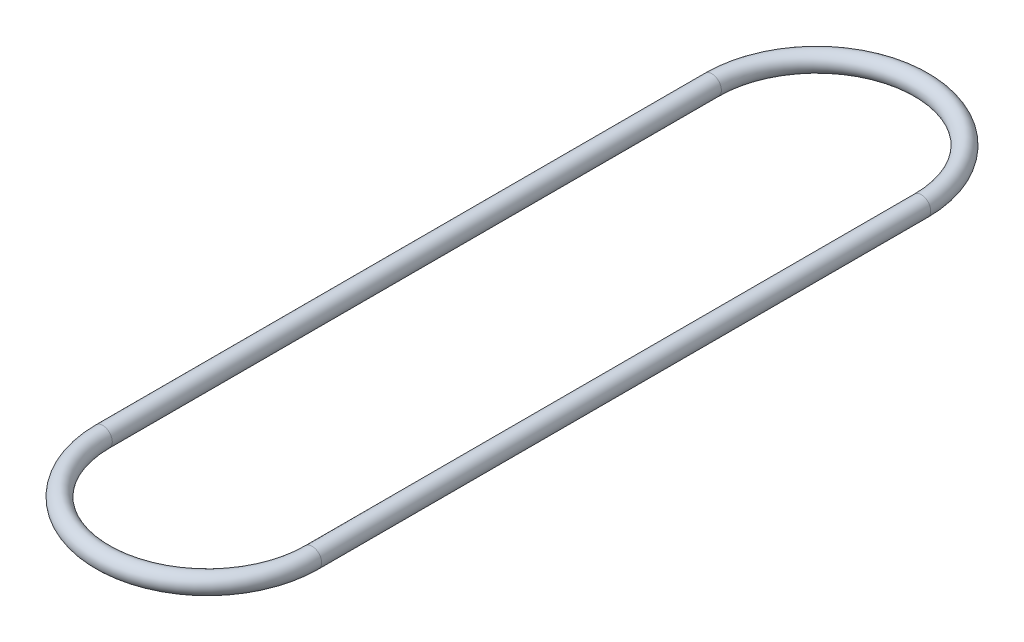
SolidWorks part; units mm, degrees
ref_plane "Front" through (0, 0, 0) normal (0, 0, 1) x (1, 0, 0)
ref_plane "Top" through (0, 0, 0) normal (0, 1, 0) x (1, 0, 0)
ref_plane "Right" through (0, 0, 0) normal (1, 0, 0) x (0, 0, -1)
sketch "Sketch1" plane through (0, 0, 0) normal (0, 0, 1) x (1, 0, 0)
  circle A0 centre (0, 0) radius 3.175
  dimension "D1" = 6.35
sketch "Sketch2" plane through (0, 0, 0) normal (0, 1, 0) x (1, 0, 0)
  line L0 (34.925, 0) -> (34.925, 203.2) construction
  line L1 (0, 0) -> (0, 203.2)
  line L2 (69.85, 0) -> (69.85, 203.2)
  arc A0 (0, 0) -> (69.85, 0) centre (34.925, 0) ccw
  arc A1 (69.85, 203.2) -> (0, 203.2) centre (34.925, 203.2) ccw
  point P2 (34.925, 101.6)
  dimension "D1" = 69.85
  dimension "D2" = 203.2
sweep "Sweep1" add profiles "Sketch1" path "Sketch2"
ref_axis "Axis1" through (34.925, 0, -203.2) along (0, 1, 0)
ref_axis "Axis2" through (34.925, 0, 0) along (0, 1, 0)
